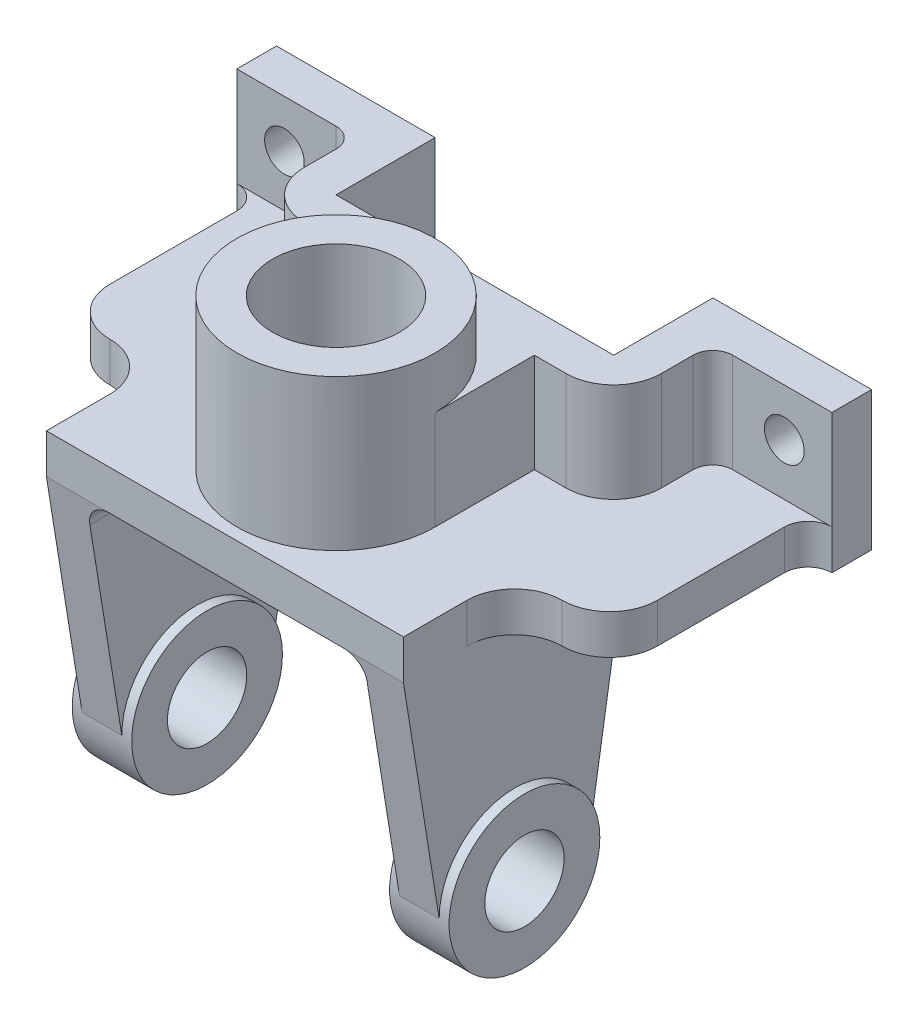
SolidWorks part; units mm, degrees
ref_plane "Front Plane" through (0, 0, 0) normal (0, 0, 1) x (1, 0, 0)
ref_plane "Top Plane" through (0, 0, 0) normal (0, 1, 0) x (1, 0, 0)
ref_plane "Right Plane" through (0, 0, 0) normal (1, 0, 0) x (0, 0, -1)
sketch "Sketch1" plane through (0, 0, 0) normal (0, 1, 0) x (1, 0, 0)
  line L0 (-45, 0) -> (45, 0)
  line L1 (0, 0) -> (0, 88) construction
  line L2 (0, 63) -> (35, 63)
  line L3 (35, 63) -> (35, 88)
  line L4 (35, 88) -> (75, 88)
  line L5 (25, 53) -> (45, 53)
  line L6 (45, 53) -> (45, 78)
  line L7 (45, 78) -> (75, 78)
  line L8 (25, 28) -> (25, 53)
  line L9 (0, 53) -> (45, 53) construction
  line L10 (45, 0) -> (45, 28)
  line L11 (45, 28) -> (69, 28)
  line L12 (69, 28) -> (69, 78)
  line L13 (75, 88) -> (75, 78)
  line L14 (-45, 0) -> (-45, 28)
  line L15 (-45, 28) -> (-69, 28)
  line L16 (-69, 28) -> (-69, 78)
  line L17 (-25, 28) -> (-25, 53)
  line L18 (-25, 53) -> (-45, 53)
  line L19 (-45, 53) -> (-45, 78)
  line L20 (-75, 88) -> (-75, 78)
  line L21 (-45, 78) -> (-75, 78)
  line L22 (-35, 88) -> (-75, 88)
  line L23 (-35, 63) -> (-35, 88)
  line L24 (0, 63) -> (-35, 63)
  circle A0 centre (0, 28) radius 16
  circle A1 centre (0, 28) radius 25
  point P3 (0, 0)
  dimension "D3" = 60
  dimension "D4" = 32
  dimension "D5" = 50
  dimension "D1" = 90
  dimension "D2" = 88
  dimension "D6" = 25
  dimension "D7" = 35
  dimension "D8" = 40
  dimension "D10" = 6
  dimension "D9" = 10
extrude "Boss-Extrude1" add sketch "Sketch1" along normal blind 10 contours A1 L17 L18 L19 L21 L16 L15 L14 L0 L10 L11 L12 L7 L6 L5 L8 | A1 A0 | A1 L8 L5 L6 L7 L13 L4 L3 L2 L24 L23 L22 L20 L21 L19 L18 L17 region at (-43.4148, 0, -14) region at (-72, 0, -79.6155) region at (0, 0, -52.2929)
extrude "Boss-Extrude3" add sketch "Sketch1<8>" along normal blind 35 contours A1 L8 L5 L6 L7 L13 L4 L3 L2 L24 L23 L22 L20 L21 L19 L18 L17 | A1 A0 region at (-72, 0, -79.6155) region at (0, 0, -52.2929)
sketch "Sketch1<8>" plane through (0, 0, 0) normal (0, 1, 0) x (1, 0, 0) same geometry as "Sketch1"
extrude "Boss-Extrude4" add sketch "Sketch1<9>" along normal blind 48 contours A0 | A1
sketch "Sketch1<9>" plane through (0, 0, 0) normal (0, 1, 0) x (1, 0, 0) same geometry as "Sketch1"
sketch "Sketch7" plane through (45, 0, 0) normal (1, 0, 0) x (0, 0, -1)
  line L0 (28, 0) -> (28, -56) construction
  line L1 (9, -56) -> (0, 0)
  line L2 (47, -56) -> (56, 0)
  line L3 (0, 0) -> (56, 0)
  circle A0 centre (28, -56) radius 19
  circle A1 centre (28, -56) radius 10
  line M2 (0, 0) -> (28, 0)
  dimension "D2" = 20
  dimension "D3" = 38
  dimension "D1" = 66
extrude "Boss-Extrude5" add sketch "Sketch7" against normal blind 10 contours L3 L0 A0 L2 | L0 L1 A0 M2 | A0 A1 region at (45, -20.2473, -40.9453) region at (45, -20.2473, -15.0547) region at (45, -42.945, -41.055)
extrude "Boss-Extrude6" add sketch "Sketch7<5>" along normal blind 2.5 and the other way blind 12.5 from offset 0 contours A0 A1 region at (45, -37.5374, -28)
sketch "Sketch7<5>" plane through (45, 0, 0) normal (1, 0, 0) x (0, 0, -1) same geometry as "Sketch7"
fillet "Fillet1" radius 5 1 edges at (35, 0, -28)
fillet "Fillet2" radius 12 1 edges at (45, 5, -28)
fillet "Fillet3" radius 12 1 edges at (69, 5, -28)
fillet "Fillet4" radius 6 1 edges at (69, 5, -78)
fillet "Fillet5" radius 25 1 edges at (37.5, 0, -56)
mirror "Mirror2" about plane through (0, 0, 0) normal (1, 0, 0) of "Boss-Extrude6", "Boss-Extrude5"
fillet "Fillet6" radius 6 1 edges at (-35, 0, -28)
fillet "Fillet7" radius 25 1 edges at (-37, 0, -56)
fillet "Fillet8" radius 12 1 edges at (-45, 5, -28)
fillet "Fillet9" radius 12 1 edges at (-69, 5, -28)
fillet "Fillet10" radius 6 1 edges at (-69, 5, -78)
fillet "Fillet11" radius 12 1 edges at (45, 22.5, -53)
fillet "Fillet12" radius 12 1 edges at (-45, 22.5, -53)
fillet "Fillet13" radius 5 1 edges at (45, 22.5, -78)
fillet "Fillet14" radius 5 1 edges at (-45, 22.5, -78)
sketch "Sketch11" plane through (0, 0, -78) normal (0, 0, 1) x (1, 0, 0)
  line L0 (50, 35) -> (75, 35) construction
  line L1 (75, 35) -> (75, 10) construction
  circle A0 centre (63, 23) radius 5
  dimension "D1" = 10
  dimension "D3" = 12
  dimension "D2" = 12
extrude "Cut-Extrude1" cut sketch "Sketch11" against normal through all
mirror "Mirror8" about plane through (0, 0, 0) normal (1, 0, 0) of "Cut-Extrude1"
